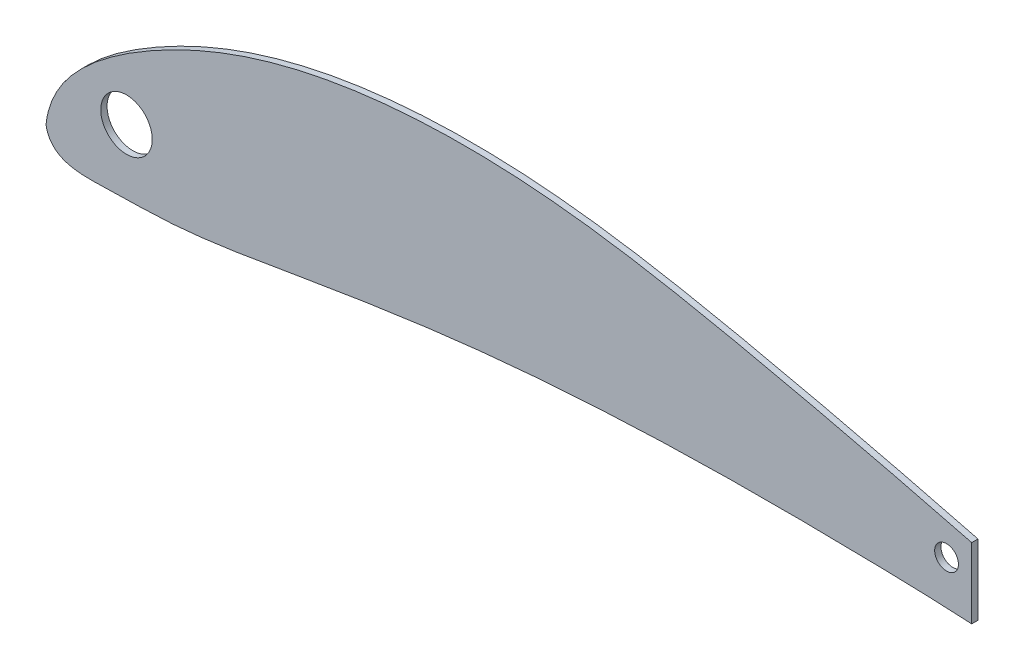
SolidWorks part; units mm, degrees
material "Balsa"
ref_plane "Front Plane" through (0, 0, 0) normal (0, 0, 1) x (1, 0, 0)
ref_plane "Top Plane" through (0, 0, 0) normal (0, 1, 0) x (1, 0, 0)
ref_plane "Right Plane" through (0, 0, 0) normal (1, 0, 0) x (0, 0, -1)
sketch "Sketch1" plane through (0, 0, 0) normal (0, 0, 1) x (1, 0, 0)
  spline S0 degree 3 poles (0.0006, 0.0001) (0.8106, 7.3592) (8.6491, 17.8566) (26.2867, 29.9752) (52.1111, 42.0692) (89.5976, 49.2908) (131.4008, 47.8848) (173.2567, 40.0411) (217.9611, 29.613) (256.9521, 19.5289) (290.3598, 8.711) (301.2732, 4.3828) (314.8169, -0.5162) (309.8463, 0.0001) knots 0 0 0 0 0.060864 0.113688 0.188609 0.312909 0.448482 0.557612 0.691544 0.852438 0.929756 0.976058 1 1 1 1
  spline S1 degree 3 poles (309.8463, 0.0001) (303.9568, 1.471) (293.9895, 2.094) (276.264, 4.5144) (260.8463, 5.4274) (235.8588, 7.8703) (205.1014, 8.8381) (157.7186, 9.0307) (110.4973, 6.1815) (66.5062, -0.5867) (36.4547, -6.0985) (15.3166, -6.1891) (1.2307, -6.9241) (0.0006, 0.0001) knots 0 0 0 0 0.057787 0.095275 0.171021 0.205339 0.335319 0.464904 0.658702 0.785512 0.893517 0.943092 1 1 1 1
extrude "Boss-Extrude1" add sketch "Sketch1" along normal blind 1.5875
sketch "Sketch2" plane through (0, 0, 1.5875) normal (0, 0, 1) x (1, 0, 0)
  circle A0 centre (20.32, 10.16) radius 6.5
  circle A1 centre (227.2963, 19.0501) radius 3
  dimension "D2" = 13
  dimension "D3" = 6
  dimension "D6" = 20.32
  dimension "D1" = 82.55
  dimension "D4" = 19.05
  dimension "D5" = 10.16
extrude "Cut-Extrude1" cut sketch "Sketch2" against normal through all
sketch "Sketch3" plane through (0, 0, 1.5875) normal (0, 0, 1) x (1, 0, 0)
  line L1 (350.4863, -6.3499) -> (233.6463, -6.3499)
  line L2 (350.4863, -6.3499) -> (350.4863, 44.4501)
  line L3 (350.4863, 44.4501) -> (233.6463, 44.4501)
  line L4 (233.6463, -6.3499) -> (233.6463, 44.4501)
  circle A0 centre (227.2963, 19.0501) radius 3 construction
  dimension "D1" = 6.35
  dimension "D2" = 116.84
  dimension "D3" = 50.8
  dimension "D4" = 44.45
extrude "Cut-Extrude2" cut sketch "Sketch3" against normal through all contours L3 L4 L1 L2
